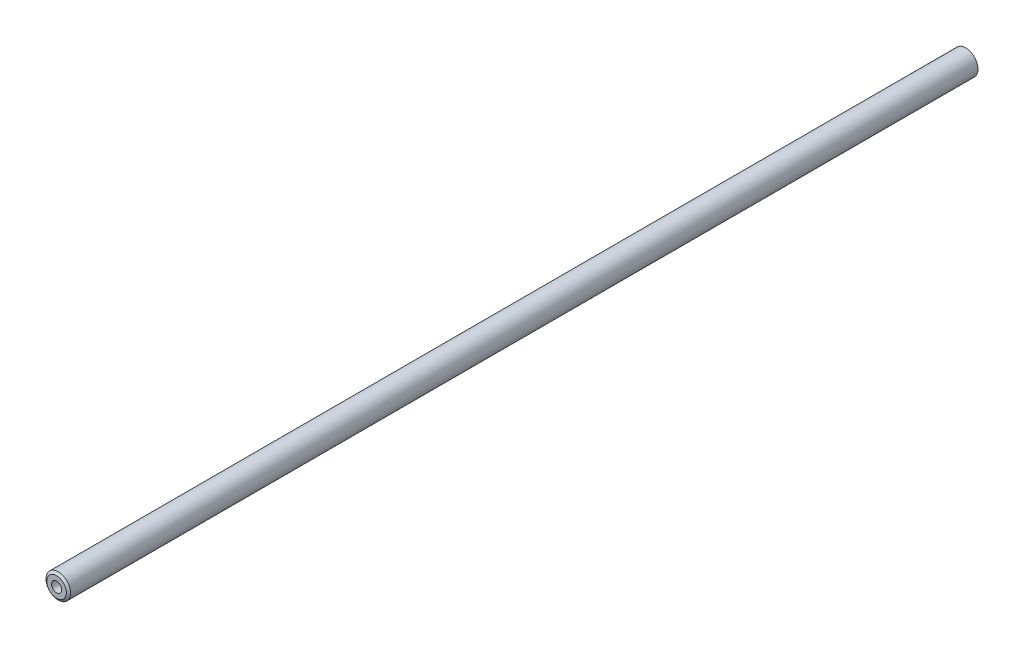
SolidWorks part; units mm, degrees
ref_plane "Front" through (0, 0, 0) normal (0, 0, 1) x (1, 0, 0)
ref_plane "Top" through (0, 0, 0) normal (0, 1, 0) x (1, 0, 0)
ref_plane "Right" through (0, 0, 0) normal (1, 0, 0) x (0, 0, -1)
sketch "Sketch22" plane through (0, 0, 0) normal (1, 0, 0) x (0, 0, -1)
  line L0 (-148.5, 0) -> (-148.5, 3.2)
  line L1 (-148.5, 3.2) -> (-147.9398, 4)
  line L2 (-147.9398, 4) -> (147.9398, 4)
  line L3 (147.9398, 4) -> (148.5, 3.2)
  line L4 (148.5, 3.2) -> (148.5, 0)
  line L5 (148.5, 0) -> (-148.5, 0)
  line L6 (148.5, 0) -> (158.5131, 0) construction
  line L8 (0, 0) -> (0, 20.8222) construction
  line L9 (-147.9398, -4) -> (147.9398, -4) construction
  dimension "Dia" = 8
  dimension "Length" = 297
  dimension "D3" = 35
  dimension "D7" = 6.4
revolve "Revolve1" add sketch "Sketch22" angle 360 about L6
ref_plane "Plane1" through (0, 0, -148.5) normal (0, 0, 1) x (1, 0, 0)
sketch "Sketch27" plane through (0, 0, -148.5) normal (0, 0, 1) x (1, 0, 0)
  circle A0 centre (0, 0) radius 4 construction
  circle A1 centre (0, 0) radius 4
curve "Helix/Spiral1" pitch 1 height 298 turns 298
sketch "Sketch28" plane through (0, 0, 0) normal (1, 0, 0) x (0, 0, -1)
  line L0 (148.5, 4) -> (149.375, 4)
  line L1 (149.375, 4) -> (149, 3.3505)
  line L2 (149, 3.3505) -> (148.875, 3.3505)
  line L3 (148.875, 3.3505) -> (148.5, 4)
  line L4 (148.6875, 3.6752) -> (149.1875, 3.6752) construction
  line L6 (-147.9398, 4) -> (147.9398, 4) construction
  dimension "D1" = 0.125
  dimension "D2" = 0.5
  dimension "D3" = 60
sweep "Cut-Sweep2" [suppressed] cut profiles "Sketch28" path "Helix/Spiral1"
sketch "Sketch29" plane through (0, 0, -148.5) normal (0, 0, 1) x (1, 0, 0)
  circle A0 centre (0, 0) radius 1.65
  dimension "D1" = 3.3
extrude "Cut-Extrude1" cut sketch "Sketch29" along normal blind 10
sketch "Sketch30" plane through (0, 0, 148.5) normal (0, 0, 1) x (1, 0, 0)
  circle A1 centre (0, 0) radius 1.65
  circle A2 centre (0, 0) radius 1.65
  dimension "D1" = 0
extrude "Cut-Extrude2" cut sketch "Sketch30" against normal blind 12
equation "\"D7@Sketch22\"=\"Dia@Sketch22\"*.8"
equation "\"D1@Sketch28\" = \"D4@Helix/Spiral1\" * .125"
equation "\"D2@Sketch28\" = \"D4@Helix/Spiral1\" * .5"
equation "\"D3@Helix/Spiral1\" = \"Length@Sketch22\" + \"D4@Helix/Spiral1\""
